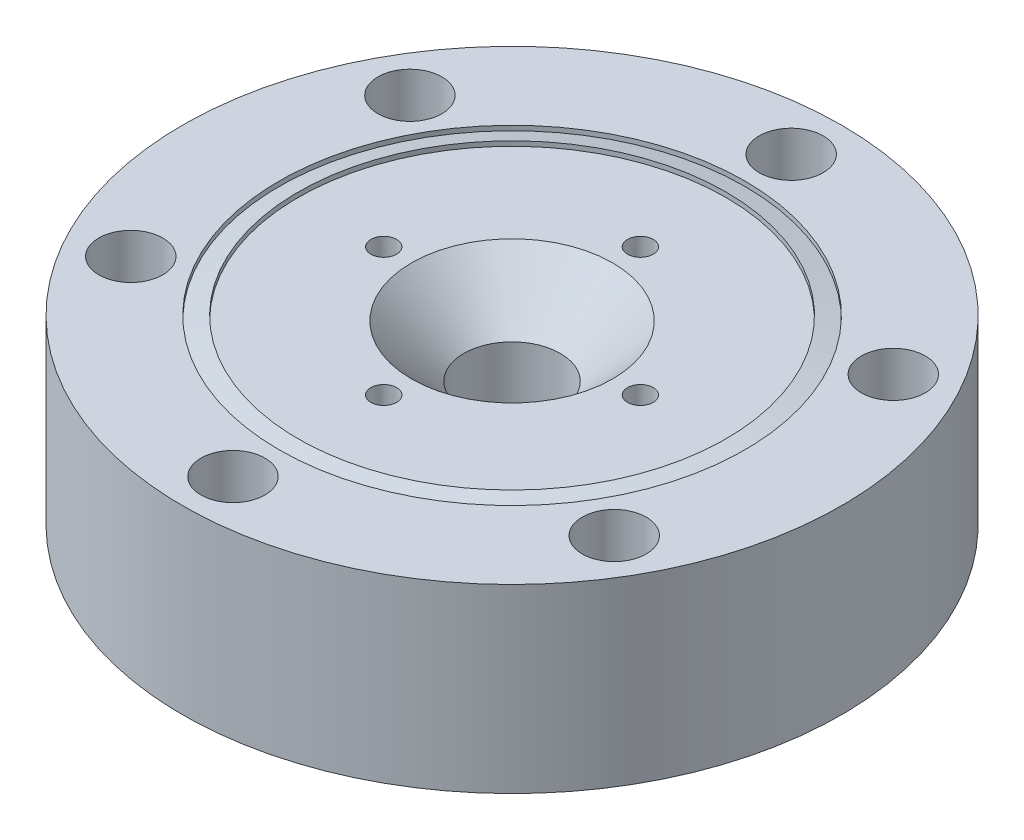
SolidWorks part; units mm, degrees
ref_plane "Front Plane" through (0, 0, 0) normal (0, 0, 1) x (1, 0, 0)
ref_plane "Top Plane" through (0, 0, 0) normal (0, 1, 0) x (1, 0, 0)
ref_plane "Right Plane" through (0, 0, 0) normal (1, 0, 0) x (0, 0, -1)
sketch "Sketch1" plane through (0, 0, 0) normal (0, 1, 0) x (1, 0, 0)
  circle A0 centre (0, 0) radius 34.671
  dimension "D1" = 69.342
extrude "Boss-Extrude1" add sketch "Sketch1" along normal blind 19.05
sketch "Sketch2" plane through (0, 0, 0) normal (0, -1, 0) x (1, 0, 0)
  point P0 (0, 0)
sketch "Sketch5" plane through (0, 0, 0) normal (0, -1, 0) x (1, 0, 0)
  circle A0 centre (0, 0) radius 5.08
  dimension "D1" = 10.16
extrude "Cut-Extrude1" cut sketch "Sketch5" against normal through all
chamfer "Chamfer1" distance 6 angle 45 1 edges at (0, 19.05, -5.08)
hole_wizard "#6-32 Tapped Hole1" positions "Sketch7" profile "Sketch6" tap size "#6-32" standard "Ansi Inch"
sketch "Sketch7" plane through (0, 19.05, 0) normal (0, 1, 0) x (-1, 0, 0)
  line L0 (0, -13.5) -> (0, 0) construction
  point P0 (0, -13.5)
  dimension "D1" = 13.5
sketch "Sketch6" plane through (0, 19.05, -13.5) normal (1, 0, 0) x (0, 0, 1)
  line L0 (0, 0) -> (0, 10.8127)
  line L1 (0, 10.8127) -> (1.3525, 10)
  line L2 (1.3525, 10) -> (1.3525, 0)
  line L5 (1.3525, 0) -> (0, 0)
  line L10 (0, 10.8127) -> (-1.3526, 10) construction
  line L11 (0, -6.35) -> (0, 107.95) construction
  dimension "Tap Drill Dia." = 2.7051
  dimension "Tap Drill Depth" = 10
  dimension "Drill Angle" = 118
cosmetic thread "Hole Thread1" parameters "D1"=7.01, "D2"=3.5052
pattern_circular "CirPattern1" count 4 over 360 about axis through (0, 19.05, 0) along (0, -1, 0) of "#6-32 Tapped Hole1"
sketch "Sketch8" plane through (0, 19.05, 0) normal (0, 1, 0) x (1, 0, 0)
  circle A0 centre (0, 29.3624) radius 3.3655
  dimension "D1" = 6.731
  dimension "D2" = 29.3624
extrude "Cut-Extrude2" cut sketch "Sketch8" against normal through all
pattern_circular "CirPattern2" count 6 over 360 about axis through (0, 19.05, 0) along (0, -1, 0) of "Cut-Extrude2"
sketch "Sketch9" plane through (0, 0, 0) normal (0, 0, 1) x (1, 0, 0)
  line L0 (0, -2.5708) -> (0, 0.5)
  line L1 (0, 0.5) -> (22.5, 0.5)
  line L2 (22.5, 0.5) -> (22.5, 0)
  line L3 (22.5, 0) -> (24.5, 0.5)
  line L4 (24.5, 0.5) -> (24.5, -7.988)
  line L5 (24.5, -7.988) -> (0, -7.988)
  line L6 (0, -7.988) -> (0, -2.5708)
  line L7 (-34.671, 0) -> (34.671, 0) construction
  dimension "D1" = 0.5
  dimension "D2" = 24.5
  dimension "D3" = 2
revolve "Cut-Revolve1" cut sketch "Sketch9" angle 360 about L0
ref_plane "Plane1" through (0, 9.525, 0) normal (0, -1, 0) x (1, 0, 0)
mirror "Mirror1" about plane through (0, 9.525, 0) normal (0, -1, 0) of "Cut-Revolve1"
